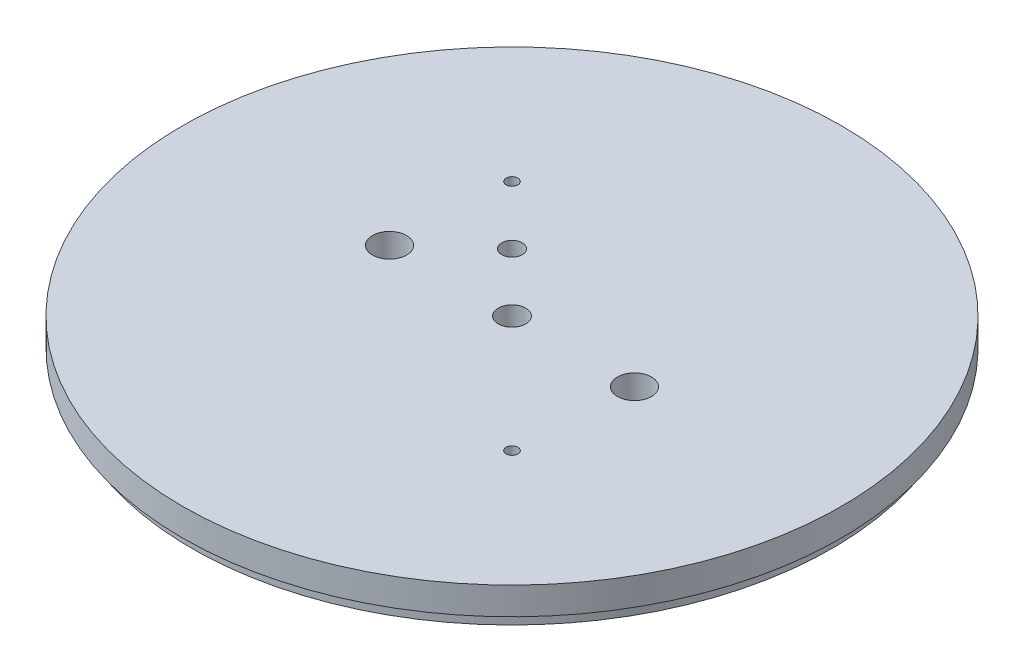
SolidWorks part; units mm, degrees
ref_plane "Front Plane" through (0, 0, 0) normal (0, 0, 1) x (1, 0, 0)
ref_plane "Top Plane" through (0, 0, 0) normal (0, 1, 0) x (1, 0, 0)
ref_plane "Right Plane" through (0, 0, 0) normal (1, 0, 0) x (0, 0, -1)
sketch "Sketch1" plane through (0, 0, 0) normal (0, 1, 0) x (1, 0, 0)
  line L0 (0, -76.2) -> (0, 76.2) construction
  line L1 (-76.2, 0) -> (76.2, 0) construction
  line L2 (-26.9408, 26.9408) -> (0, 0) construction
  line L3 (0, 56.7387) -> (0, 29.6936) construction
  line L4 (3.6407, 56.7387) -> (3.6407, 29.6936) construction
  line L5 (-3.6407, 56.7387) -> (-3.6407, 29.6936) construction
  line L6 (0, -56.7387) -> (0, -29.6936) construction
  line L7 (3.6407, -56.7387) -> (3.6407, -29.6936) construction
  line L8 (-3.6407, -56.7387) -> (-3.6407, -29.6936) construction
  line L9 (-53.8815, -53.8815) -> (54.3236, 54.3236) construction
  circle A0 centre (0, 0) radius 76.2
  circle A1 centre (0, 0) radius 3.175
  circle A2 centre (28.321, 0) radius 3.937
  circle A3 centre (-28.321, 0) radius 3.937
  circle A4 centre (-26.9408, 26.9408) radius 1.3589
  arc A6 (3.6407, 56.7387) -> (-3.6407, 56.7387) centre (0, 56.7387) ccw construction
  arc A7 (-3.6407, 29.6936) -> (3.6407, 29.6936) centre (0, 29.6936) ccw construction
  arc A8 (3.6407, -56.7387) -> (-3.6407, -56.7387) centre (0, -56.7387) cw construction
  arc A9 (-3.6407, -29.6936) -> (3.6407, -29.6936) centre (0, -29.6936) cw construction
  circle A10 centre (26.9408, -26.9408) radius 1.3589
  circle A11 centre (-13.4704, 13.4704) radius 2.3813
  point P16 (0, 43.2162)
  point P19 (0, 0)
  point P26 (0, -43.2162)
  point P35 (0, 0)
  point P36 (0, 0)
  dimension "D1" = 152.4
  dimension "D2" = 6.35
  dimension "D3" = 7.874
  dimension "D5" = 2.7178
  dimension "D8" = 4.7625
  dimension "D4" = 45
  dimension "D6" = 38.1
  dimension "D7" = 45
  dimension "D9" = 28.321
extrude "Boss-Extrude1" add sketch "Sketch1" along normal blind 9.525
sketch "Sketch2" plane through (0, 0, 0) normal (0, -1, 0) x (1, 0, 0)
  circle A0 centre (0, 0) radius 76.2
  circle A1 centre (0, 0) radius 74.041
  dimension "D1" = 152.4
  dimension "D2" = 148.082
extrude "Cut-Extrude1" cut sketch "Sketch2" against normal blind 3.175
sketch "Sketch3" plane through (0, 9.525, 0) normal (0, 1, 0) x (1, 0, 0)
  line L0 (0, 76.2) -> (0, -76.2) construction
  line L1 (-76.2, 0) -> (76.2, 0) construction
  line L2 (0, 34.798) -> (0, 13.97) construction
  line L3 (3.2385, 34.798) -> (3.2385, 13.97)
  line L4 (-3.2385, 34.798) -> (-3.2385, 13.97)
  line L5 (0, -34.798) -> (0, -13.97) construction
  line L6 (3.2385, -34.798) -> (3.2385, -13.97)
  line L7 (-3.2385, -34.798) -> (-3.2385, -13.97)
  circle A0 centre (0, 0) radius 76.2 construction
  arc A1 (3.2385, 34.798) -> (-3.2385, 34.798) centre (0, 34.798) ccw
  arc A2 (-3.2385, 13.97) -> (3.2385, 13.97) centre (0, 13.97) ccw
  arc A3 (3.2385, -34.798) -> (-3.2385, -34.798) centre (0, -34.798) cw
  arc A4 (-3.2385, -13.97) -> (3.2385, -13.97) centre (0, -13.97) cw
  point P7 (0, 13.97)
  point P8 (0, 34.798)
  point P12 (0, 24.384)
  point P17 (0, 0)
  point P20 (0, -24.384)
  point P25 (0, -34.798)
  point P26 (0, -13.97)
  dimension "D1" = 13.97
  dimension "D2" = 20.828
  dimension "D3" = 6.477
extrude "Cut-Extrude2" cut sketch "Sketch3" against normal blind 3.556 from offset 5.969 offset against normal yes
equation "\"leadDist\"=1.5"
